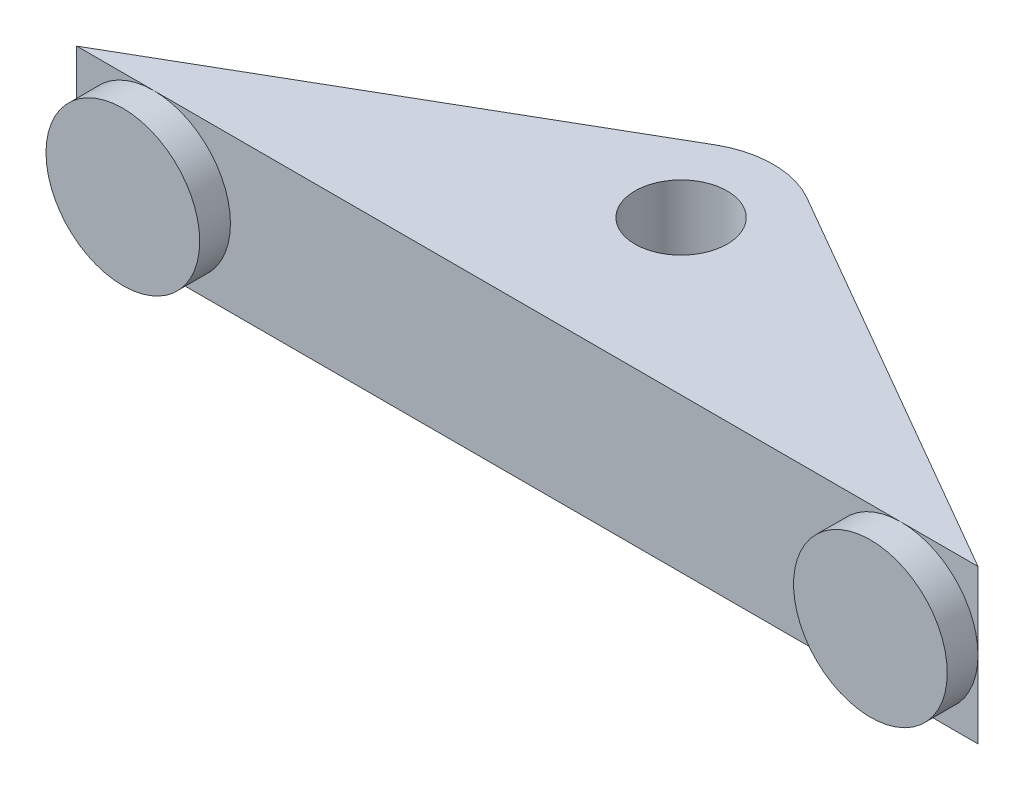
SolidWorks part; units mm, degrees
ref_plane "Спереди" through (0, 0, 0) normal (0, 0, 1) x (1, 0, 0)
ref_plane "Сверху" through (0, 0, 0) normal (0, 1, 0) x (1, 0, 0)
ref_plane "Справа" through (0, 0, 0) normal (1, 0, 0) x (0, 0, -1)
sketch "Эскиз1" plane through (0, 0, 0) normal (0, 1, 0) x (1, 0, 0)
  circle A0 centre (0, 0) radius 1.5
  circle A1 centre (0, 0) radius 3
  dimension "D1" = 3
  dimension "D2" = 6
extrude "Бобышка-Вытянуть1" add sketch "Эскиз1" along normal blind 5
sketch "Эскиз2" plane through (0, 5, 0) normal (0, 1, 0) x (1, 0, 0)
  line L0 (-1.5, 2.5981) -> (-14.6603, -5)
  line L1 (-14.6603, -5) -> (14.6603, -5)
  line L2 (14.6603, -5) -> (1.5, 2.5981)
  line L3 (-1.5, 2.5981) -> (1.5, 2.5981)
  circle A0 centre (0, 0) radius 3 construction
  circle A1 centre (0, 0) radius 1.5 construction
  circle A2 centre (0, 0) radius 1.5
  dimension "D2" = 5
  dimension "D1" = 120
extrude "Бобышка-Вытянуть2" add sketch "Эскиз2" against normal through all
sketch "Эскиз3" plane through (0, 0, 5) normal (0, 0, 1) x (1, 0, 0)
  line L0 (-14.6603, 2.5) -> (14.6603, 2.5) construction
  line L1 (-14.6603, 0) -> (-14.6603, 5) construction
  line L2 (14.6603, 0) -> (14.6603, 5) construction
  line L3 (-14.6603, 0) -> (14.6603, 0) construction
  circle A0 centre (-12.1603, 2.5) radius 2.5
  circle A1 centre (12.1603, 2.5) radius 2.5
extrude "Бобышка-Вытянуть3" add sketch "Эскиз3" along normal blind 1
